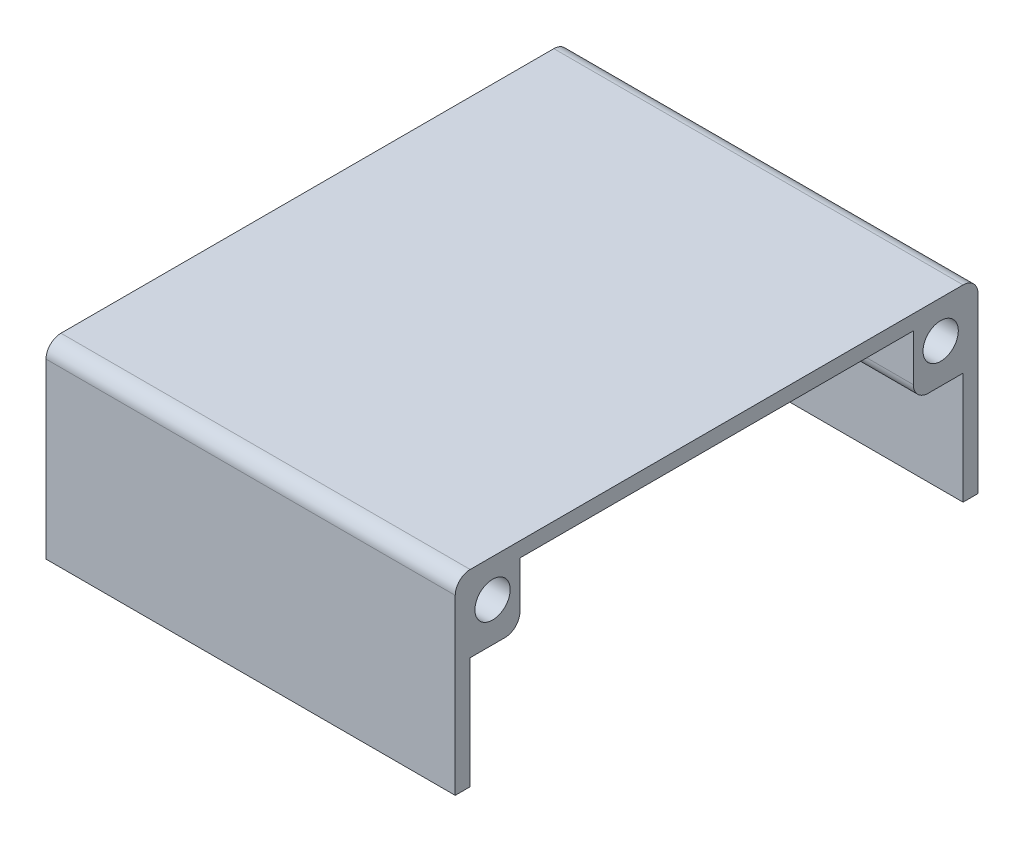
SolidWorks part; units mm, degrees
ref_plane "Front Plane" through (0, 0, 0) normal (0, 0, 1) x (1, 0, 0)
ref_plane "Top Plane" through (0, 0, 0) normal (0, 1, 0) x (1, 0, 0)
ref_plane "Right Plane" through (0, 0, 0) normal (1, 0, 0) x (0, 0, -1)
sketch "Sketch1" plane through (0, 0, 0) normal (1, 0, 0) x (0, 0, -1)
  line L1 (-44.4525, -16.002) -> (44.4525, -16.002)
  line L2 (-44.4525, -16.002) -> (-44.4525, 16.002)
  line L3 (-44.4525, 16.002) -> (44.4525, 16.002)
  line L4 (44.4525, -16.002) -> (44.4525, 16.002)
  line L5 (-44.4525, -16.002) -> (44.4525, 16.002) construction
  line L6 (-44.4525, 16.002) -> (44.4525, -16.002) construction
  point P0 (0, 0)
  dimension "D1" = 88.905
  dimension "D2" = 32.004
extrude "Boss-Extrude1" add sketch "Sketch1" along normal blind 69.596
fillet "Fillet1" radius 2.54 1 edges at (34.798, 16.002, -44.4525)
fillet "Fillet2" radius 2.54 1 edges at (34.798, 16.002, 44.4525)
sketch "Sketch13" plane through (0, 0, 0) normal (-1, 0, 0) x (0, 0, 1)
  line L0 (-44.4525, -16.002) -> (-44.4525, 13.462) construction
  line L1 (-41.9125, -16.002) -> (41.9125, -16.002)
  line L2 (-41.9125, -16.002) -> (-41.9125, 13.462)
  line L3 (-41.9125, 13.462) -> (41.9125, 13.462)
  line L4 (41.9125, -16.002) -> (41.9125, 13.462)
  line L5 (44.4525, 13.462) -> (44.4525, -16.002) construction
  line L6 (44.4525, -16.002) -> (-44.4525, -16.002) construction
  dimension "D1" = 2.54
  dimension "D2" = 2.54
  dimension "D3" = 29.464
extrude "Cut-Extrude1" cut sketch "Sketch13" against normal blind 90
sketch "Sketch15" plane through (0, 0, 0) normal (-1, 0, 0) x (0, 0, 1)
  line L0 (44.4525, 13.462) -> (44.4525, -16.002) construction
  line L1 (-41.9125, 16.002) -> (41.9125, 16.002) construction
  line L2 (41.9125, 13.462) -> (-41.9125, 13.462) construction
  line L3 (33.4525, 13.462) -> (41.9125, 13.462)
  line L4 (33.4525, 13.462) -> (33.4525, 3.002)
  line L5 (33.4525, 3.002) -> (41.9125, 3.002)
  line L6 (41.9125, 13.462) -> (41.9125, 3.002)
  line L7 (41.9125, -16.002) -> (41.9125, 13.462) construction
  circle A0 centre (38.1025, 9.652) radius 3
  dimension "D1" = 6.35
  dimension "D2" = 6
  dimension "D3" = 6.35
  dimension "D4" = 13
  dimension "D5" = 11
sketch "Sketch19" plane through (0, 0, 0) normal (-1, 0, 0) x (0, 0, 1)
  line L3 (-41.9125, 16.002) -> (41.9125, 16.002) construction
  line L4 (-44.4525, -16.002) -> (-44.4525, 13.462) construction
  line L8 (-41.9125, 13.462) -> (-33.4525, 13.462)
  line L9 (-41.9125, 13.462) -> (-41.9125, 3.002)
  line L10 (-41.9125, 3.002) -> (-33.4525, 3.002)
  line L11 (-33.4525, 13.462) -> (-33.4525, 3.002)
  line L20 (33.4525, 3.002) -> (41.9125, 3.002) construction
  line L21 (33.4525, 13.462) -> (33.4525, 3.002) construction
  circle A0 centre (-38.1025, 9.652) radius 3
  dimension "D1" = 6.35
  dimension "D2" = 6
  dimension "D3" = 6.35
extrude "Boss-Extrude8" add sketch "Sketch15" against normal blind 69.596
extrude "Boss-Extrude9" add sketch "Sketch19" against normal blind 69.596
fillet "Fillet3" radius 2.54 2 edges at (34.798, 3.002, 33.4525) (34.798, 3.002, -33.4525)
